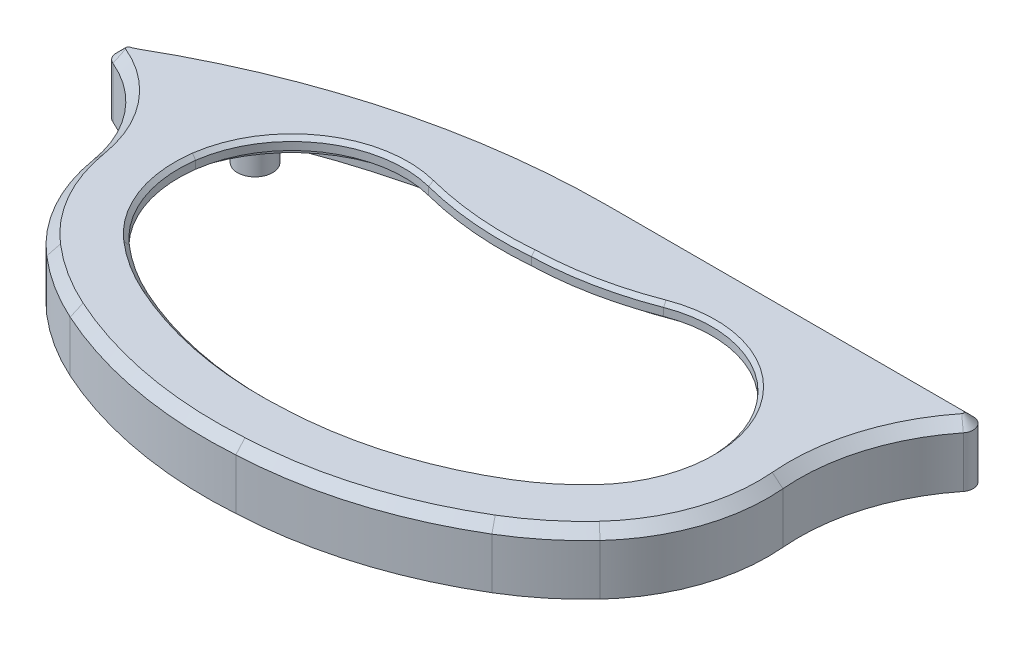
SolidWorks part; units mm, degrees
ref_plane "Front Plane" through (0, 0, 0) normal (0, 0, 1) x (1, 0, 0)
ref_plane "Top Plane" through (0, 0, 0) normal (0, 1, 0) x (1, 0, 0)
ref_plane "Right Plane" through (0, 0, 0) normal (1, 0, 0) x (0, 0, -1)
sketch "Case_Line" plane through (0, 0, 0) normal (0, 1, 0) x (1, 0, 0)
  line L0 (80.0987, 83.4768) -> (-10.614, 83.4768) construction
  arc A0 (85.0987, 88.4768) -> (80.0987, 83.4768) centre (80.0987, 88.4768) cw construction
  arc A2 (-113.6793, 59.6258) -> (-106.8525, 57.7833) centre (-109.3447, 62.1179) ccw construction
  arc A6 (-10.614, 83.4768) -> (-106.8525, 57.7833) centre (-10.614, -109.6066) ccw construction
sketch "Wrest" plane through (0, 0, 0) normal (0, 1, 0) x (1, 0, 0)
  line L6 (-10.569, 65.8598) -> (-6.2316, -9.4162) construction
  line L7 (-10.569, 65.8598) -> (16.1282, 71.2217) construction
  line L8 (16.1282, 71.2217) -> (60.9608, 48.0555) construction
  line L9 (60.9608, 48.0555) -> (52.5888, 15.0143) construction
  line L10 (52.5888, 15.0143) -> (39.5302, 4.389) construction
  line L11 (39.5302, 4.389) -> (-6.2316, -9.4162) construction
  line L14 (80.0987, 83.4768) -> (-10.614, 83.4768) construction
  line L19 (-74.9013, 38.0401) -> (-74.9013, -63.0808) construction
  line L21 (-74.9013, 105.4768) -> (-74.9013, 87.4768) construction
  arc A10 (-10.569, 65.8598) -> (16.1282, 71.2217) centre (-12.89, 146.5605) ccw construction
  arc A11 (16.1282, 71.2217) -> (60.9608, 48.0555) centre (28.2576, 39.7306) cw construction
  arc A12 (60.9608, 48.0555) -> (52.5888, 15.0143) centre (26.348, 39.2445) cw construction
  arc A13 (52.5888, 15.0143) -> (39.5302, 4.389) centre (8.9509, 55.3086) cw construction
  arc A14 (39.5302, 4.389) -> (-6.2316, -9.4162) centre (-10.6307, 87.9151) cw construction
  arc A15 (-53.2763, -0.9584) -> (-6.2316, -9.4162) centre (-13.0408, 87.7763) ccw construction
  arc A16 (-67.4688, 8.0967) -> (-53.2763, -0.9584) centre (-28.7477, 53.1364) ccw construction
  arc A17 (-79.5804, 39.9577) -> (-67.4688, 8.0967) centre (-44.1846, 35.1805) ccw construction
  arc A18 (-37.7053, 68.1198) -> (-79.5804, 39.9577) centre (-46.1374, 35.444) ccw construction
  arc A19 (-10.569, 65.8598) -> (-37.7053, 68.1198) centre (-17.5323, 146.293) cw construction
  arc A20 (12.5339, 80.5534) -> (70.6518, 50.5225) centre (28.2576, 39.7306) cw construction
  arc A24 (-10.2812, 60.8661) -> (17.9253, 66.5558) centre (-12.89, 146.5605) ccw
  arc A50 (70.6518, 50.5225) -> (59.9357, 8.2303) centre (26.348, 39.2445) cw construction
  arc A51 (59.9357, 8.2303) -> (44.6786, -4.1838) centre (8.9509, 55.3086) cw construction
  arc A53 (44.6786, -4.1838) -> (-5.6564, -19.4003) centre (-10.6307, 87.9151) cw construction
  arc A54 (-57.4059, -10.0658) -> (-5.6564, -19.4003) centre (-13.0408, 87.7763) ccw construction
  arc A58 (-73.9879, 0.5138) -> (-57.4059, -10.0658) centre (-28.7477, 53.1364) ccw construction
  arc A71 (17.9253, 66.5558) -> (56.1154, 46.8221) centre (28.2576, 39.7306) cw
  arc A72 (56.1154, 46.8221) -> (48.9153, 18.4063) centre (26.348, 39.2445) cw
  arc A73 (48.9153, 18.4063) -> (36.9561, 8.6755) centre (8.9509, 55.3086) cw
  arc A74 (36.9561, 8.6755) -> (-6.5193, -4.424) centre (-10.6307, 87.9151) cw
  arc A75 (-51.2115, 3.5954) -> (-6.5193, -4.424) centre (-13.0408, 87.7763) ccw
  arc A76 (-64.2092, 11.8882) -> (-51.2115, 3.5954) centre (-28.7477, 53.1364) ccw
  arc A77 (-74.6253, 39.2889) -> (-64.2092, 11.8882) centre (-44.1846, 35.1805) ccw
  arc A78 (-38.9546, 63.2784) -> (-74.6253, 39.2889) centre (-46.1374, 35.444) ccw
  arc A79 (-10.2812, 60.8661) -> (-38.9546, 63.2784) centre (-17.5323, 146.293) cw
  arc A80 (-89.4906, 41.2952) -> (-73.9879, 0.5138) centre (-44.1846, 35.1805) ccw construction
  arc A81 (-35.2066, 77.8026) -> (-89.4906, 41.2952) centre (-46.1374, 35.444) ccw construction
  arc A82 (-11.1445, 75.8479) -> (-35.2066, 77.8026) centre (-17.5323, 146.293) cw construction
  arc A83 (-11.1445, 75.8479) -> (12.5339, 80.5534) centre (-12.89, 146.5605) ccw construction
  arc A85 (-10.614, 83.4768) -> (-106.8525, 57.7833) centre (-10.614, -109.6066) ccw construction
  dimension "D2" = 27.2303
  dimension "D7" = 80.7341
  dimension "D15" = 5
  dimension "D1" = 75.4008
  dimension "D3" = 50.4642
  dimension "D4" = 34.0854
  dimension "D5" = 47.7989
  dimension "D6" = 16.8352
  dimension "D8" = 103.108
  dimension "D9" = 98.059
  dimension "D10" = 76.51
  dimension "D11" = 10
sketch "Sketch6" plane through (0, 0, 0) normal (0, 1, 0) x (1, 0, 0)
  line L0 (84.9594, 87.3051) -> (70.7917, 28.5311) construction
  line L1 (-88.1859, 17.3185) -> (-113.6272, 59.5372) construction
  line L2 (80.0987, 83.4768) -> (-10.614, 83.4768)
  arc A0 (-73.9879, 0.5138) -> (-57.4059, -10.0658) centre (-28.7477, 53.1364) ccw construction
  arc A1 (59.9357, 8.2303) -> (70.6518, 50.5225) centre (26.348, 39.2445) ccw construction
  arc A2 (-113.6793, 59.6258) -> (-106.8525, 57.7833) centre (-109.3447, 62.1179) ccw construction
  arc A3 (80.0987, 83.4768) -> (85.0987, 88.4768) centre (80.0987, 88.4768) ccw construction
  arc A4 (80.1793, 83.4775) -> (82.5748, 78.6094) centre (80.2278, 80.4779) cw
  arc A5 (-107.9166, 57.3262) -> (-108.2193, 51.6843) centre (-107.0597, 54.4512) ccw
  circle A6 centre (80.2278, 80.4779) radius 3 construction
  arc A7 (-5.6564, -19.4003) -> (44.6786, -4.1838) centre (-10.6307, 87.9151) ccw construction
  arc A8 (59.9357, 8.2303) -> (71.8718, 43.1263) centre (26.4104, 39.1869) ccw
  arc A9 (82.5748, 78.6094) -> (71.8718, 43.1263) centre (121.7206, 47.4458) ccw
  circle A10 centre (-107.0597, 54.4512) radius 3 construction
  arc A11 (-57.4059, -10.0658) -> (-5.6564, -19.4003) centre (-13.0408, 87.7763) ccw construction
  arc A12 (-108.2193, 51.6843) -> (-89.2905, 27.7324) centre (-120.4115, 22.5936) cw
  arc A13 (-89.4906, 41.2952) -> (-73.9879, 0.5138) centre (-44.1846, 35.1805) ccw construction
  arc A14 (-73.9879, 0.5138) -> (-89.2905, 27.7324) centre (-44.1846, 35.1805) cw
  arc A15 (-73.9879, 0.5138) -> (-57.4059, -10.0658) centre (-28.7477, 53.1364) ccw
  arc A16 (80.1793, 83.4775) -> (80.0987, 83.4768) centre (80.0987, 88.4768) cw
  arc A21 (-57.4059, -10.0658) -> (-5.6564, -19.4003) centre (-13.0408, 87.7763) ccw
  arc A22 (59.9357, 8.2303) -> (44.6786, -4.1838) centre (8.9509, 55.3086) cw
  arc A23 (44.6786, -4.1838) -> (-5.6564, -19.4003) centre (-10.6307, 87.9151) cw
  arc A24 (70.6518, 50.5225) -> (12.5339, 80.5534) centre (28.2576, 39.7306) ccw construction
  arc A25 (-107.9166, 57.3262) -> (-106.8525, 57.7833) centre (-109.3447, 62.1179) ccw
  arc A26 (-106.8525, 57.7833) -> (-10.614, 83.4768) centre (-10.614, -109.6066) cw
  dimension "D1" = 3
extrude "Top_plane" add sketch "Sketch6" against normal blind 3
sketch "Sketch9" plane through (0, 0, 0) normal (0, 1, 0) x (1, 0, 0)
  arc A20 (-10.2812, 60.8661) -> (17.9253, 66.5558) centre (-12.89, 146.5605) ccw
  arc A21 (56.1154, 46.8221) -> (17.9253, 66.5558) centre (28.2576, 39.7306) ccw
  arc A22 (48.9153, 18.4063) -> (56.1154, 46.8221) centre (26.348, 39.2445) ccw
  arc A23 (36.9561, 8.6755) -> (48.9153, 18.4063) centre (8.9509, 55.3086) ccw
  arc A24 (-6.5193, -4.424) -> (36.9561, 8.6755) centre (-10.6307, 87.9151) ccw
  arc A25 (-51.2115, 3.5954) -> (-6.5193, -4.424) centre (-13.0408, 87.7763) ccw
  arc A26 (-64.2092, 11.8882) -> (-51.2115, 3.5954) centre (-28.7477, 53.1364) ccw
  arc A27 (-74.6253, 39.2889) -> (-64.2092, 11.8882) centre (-44.1846, 35.1805) ccw
  arc A28 (-38.9546, 63.2784) -> (-74.6253, 39.2889) centre (-46.1374, 35.444) ccw
  arc A29 (-38.9546, 63.2784) -> (-10.2812, 60.8661) centre (-17.5323, 146.293) ccw
  arc A30 (-10.2812, 60.8661) -> (17.9253, 66.5558) centre (-12.89, 146.5605) ccw
  arc A31 (56.1154, 46.8221) -> (17.9253, 66.5558) centre (28.2576, 39.7306) ccw
  arc A32 (48.9153, 18.4063) -> (56.1154, 46.8221) centre (26.348, 39.2445) ccw
  arc A33 (36.9561, 8.6755) -> (48.9153, 18.4063) centre (8.9509, 55.3086) ccw
  arc A34 (-6.5193, -4.424) -> (36.9561, 8.6755) centre (-10.6307, 87.9151) ccw
  arc A35 (-51.2115, 3.5954) -> (-6.5193, -4.424) centre (-13.0408, 87.7763) ccw
  arc A36 (-64.2092, 11.8882) -> (-51.2115, 3.5954) centre (-28.7477, 53.1364) ccw
  arc A37 (-74.6253, 39.2889) -> (-64.2092, 11.8882) centre (-44.1846, 35.1805) ccw
  arc A38 (-38.9546, 63.2784) -> (-74.6253, 39.2889) centre (-46.1374, 35.444) ccw
  arc A39 (-38.9546, 63.2784) -> (-10.2812, 60.8661) centre (-17.5323, 146.293) ccw
  dimension "D1" = 0
extrude "Pillow_hole" cut sketch "Sketch9" against normal through all
chamfer "Pillow_chamfer" distance 1 angle 45 10 edges at (16.0353, 0, 0.5854) (43.2822, 0, -13.115) (56.1237, 0, -31.6999) (4.0625, 0, -62.5191) (41.4538, 0, -65.2689) (-29.3655, 0, 3.2014) (-58.0057, 0, -7.2789) (-24.7198, 0, -60.8607) (-72.8968, 0, -24.2659) (-62.1796, 0, -59.2977)
sketch "Sketch7" plane through (0, -3, 0) normal (0, -1, 0) x (1, 0, 0)
  line L3 (-10.614, -83.4768) -> (80.0987, -83.4768)
  line L4 (-10.614, -83.4768) -> (80.0987, -83.4768)
  arc A37 (-106.8525, -57.7833) -> (-10.614, -83.4768) centre (-10.614, 109.6066) ccw
  arc A38 (-106.8525, -57.7833) -> (-107.9166, -57.3262) centre (-109.3447, -62.1179) ccw
  arc A39 (-108.2193, -51.6843) -> (-107.9166, -57.3262) centre (-107.0597, -54.4512) ccw
  arc A40 (-108.2193, -51.6843) -> (-89.2905, -27.7324) centre (-120.4115, -22.5936) ccw
  arc A41 (-73.9879, -0.5138) -> (-89.2905, -27.7324) centre (-44.1846, -35.1805) ccw
  arc A42 (-57.4059, 10.0658) -> (-73.9879, -0.5138) centre (-28.7477, -53.1364) ccw
  arc A43 (-5.6564, 19.4003) -> (-57.4059, 10.0658) centre (-13.0408, -87.7763) ccw
  arc A44 (44.6786, 4.1838) -> (-5.6564, 19.4003) centre (-10.6307, -87.9151) ccw
  arc A45 (59.9357, -8.2303) -> (44.6786, 4.1838) centre (8.9509, -55.3086) ccw
  arc A46 (71.8718, -43.1263) -> (59.9357, -8.2303) centre (26.4104, -39.1869) ccw
  arc A47 (71.8718, -43.1263) -> (82.5748, -78.6094) centre (121.7206, -47.4458) ccw
  arc A48 (80.1793, -83.4775) -> (82.5748, -78.6094) centre (80.2278, -80.4779) ccw
  arc A49 (80.1793, -83.4775) -> (80.0987, -83.4768) centre (80.0987, -88.4768) ccw
  arc A50 (-106.8525, -57.7833) -> (-10.614, -83.4768) centre (-10.614, 109.6066) ccw
  arc A51 (-106.8525, -57.7833) -> (-107.9166, -57.3262) centre (-109.3447, -62.1179) ccw
  arc A52 (-108.2193, -51.6843) -> (-107.9166, -57.3262) centre (-107.0597, -54.4512) ccw
  arc A53 (-108.2193, -51.6843) -> (-89.2905, -27.7324) centre (-120.4115, -22.5936) ccw
  arc A54 (-73.9879, -0.5138) -> (-89.2905, -27.7324) centre (-44.1846, -35.1805) ccw
  arc A55 (-57.4059, 10.0658) -> (-73.9879, -0.5138) centre (-28.7477, -53.1364) ccw
  arc A56 (-5.6564, 19.4003) -> (-57.4059, 10.0658) centre (-13.0408, -87.7763) ccw
  arc A57 (44.6786, 4.1838) -> (-5.6564, 19.4003) centre (-10.6307, -87.9151) ccw
  arc A58 (59.9357, -8.2303) -> (44.6786, 4.1838) centre (8.9509, -55.3086) ccw
  arc A59 (71.8718, -43.1263) -> (59.9357, -8.2303) centre (26.4104, -39.1869) ccw
  arc A60 (71.8718, -43.1263) -> (82.5748, -78.6094) centre (121.7206, -47.4458) ccw
  arc A61 (80.1793, -83.4775) -> (82.5748, -78.6094) centre (80.2278, -80.4779) ccw
  arc A62 (80.1793, -83.4775) -> (80.0987, -83.4768) centre (80.0987, -88.4768) ccw
  arc A188 (-53.2763, 0.9584) -> (-67.4688, -8.0967) centre (-28.7477, -53.1364) ccw
  arc A189 (-6.2316, 9.4162) -> (-53.2763, 0.9584) centre (-13.0408, -87.7763) ccw
  arc A190 (39.5302, -4.389) -> (-6.2316, 9.4162) centre (-10.6307, -87.9151) ccw
  arc A191 (52.5888, -15.0143) -> (39.5302, -4.389) centre (8.9509, -55.3086) ccw
  arc A192 (60.9608, -48.0555) -> (52.5888, -15.0143) centre (26.348, -39.2445) ccw
  arc A193 (16.1282, -71.2217) -> (60.9608, -48.0555) centre (28.2576, -39.7306) ccw
  arc A194 (16.1282, -71.2217) -> (-10.569, -65.8598) centre (-12.89, -146.5605) ccw
  arc A195 (-10.569, -65.8598) -> (-37.7053, -68.1198) centre (-17.5323, -146.293) ccw
  arc A196 (-79.5804, -39.9577) -> (-37.7053, -68.1198) centre (-46.1374, -35.444) ccw
  arc A197 (-67.4688, -8.0967) -> (-79.5804, -39.9577) centre (-44.1846, -35.1805) ccw
  arc A198 (-53.2763, 0.9584) -> (-67.4688, -8.0967) centre (-28.7477, -53.1364) ccw
  arc A199 (-6.2316, 9.4162) -> (-53.2763, 0.9584) centre (-13.0408, -87.7763) ccw
  arc A200 (39.5302, -4.389) -> (-6.2316, 9.4162) centre (-10.6307, -87.9151) ccw
  arc A201 (52.5888, -15.0143) -> (39.5302, -4.389) centre (8.9509, -55.3086) ccw
  arc A202 (60.9608, -48.0555) -> (52.5888, -15.0143) centre (26.348, -39.2445) ccw
  arc A203 (16.1282, -71.2217) -> (60.9608, -48.0555) centre (28.2576, -39.7306) ccw
  arc A204 (16.1282, -71.2217) -> (-10.569, -65.8598) centre (-12.89, -146.5605) ccw
  arc A205 (-10.569, -65.8598) -> (-37.7053, -68.1198) centre (-17.5323, -146.293) ccw
  arc A206 (-79.5804, -39.9577) -> (-37.7053, -68.1198) centre (-46.1374, -35.444) ccw
  arc A207 (-67.4688, -8.0967) -> (-79.5804, -39.9577) centre (-44.1846, -35.1805) ccw
  dimension "D1" = 0
  dimension "D2" = 0
extrude "Wrest_socket" add sketch "Sketch7" along normal blind 4
sketch "Sketch8" plane through (0, -7, 0) normal (0, -1, 0) x (1, 0, 0)
  line L2 (-10.614, -81.4768) -> (80.0987, -81.4768)
  line L6 (-10.614, -83.4768) -> (80.0987, -83.4768)
  line L7 (-10.614, -83.4768) -> (80.0987, -83.4768)
  arc A45 (80.2116, -81.4778) -> (80.0987, -81.4768) centre (80.0987, -88.4768) ccw
  arc A46 (80.2116, -81.4778) -> (81.0101, -79.8551) centre (80.2278, -80.4779) ccw
  arc A47 (69.8793, -42.9536) -> (81.0101, -79.8551) centre (121.7206, -47.4458) ccw
  arc A48 (69.8793, -42.9536) -> (58.4664, -9.5871) centre (26.4104, -39.1869) ccw
  arc A49 (58.4664, -9.5871) -> (43.6489, 2.4693) centre (8.9509, -55.3086) ccw
  arc A50 (43.6489, 2.4693) -> (-5.7714, 17.4035) centre (-10.6307, -87.9151) ccw
  arc A51 (-5.7714, 17.4035) -> (-56.58, 8.2443) centre (-13.0408, -87.7763) ccw
  arc A52 (-56.58, 8.2443) -> (-72.6841, -2.0304) centre (-28.7477, -53.1364) ccw
  arc A53 (-72.6841, -2.0304) -> (-87.3173, -28.0582) centre (-44.1846, -35.1805) ccw
  arc A54 (-107.4463, -53.5289) -> (-87.3173, -28.0582) centre (-120.4115, -22.5936) ccw
  arc A55 (-107.4463, -53.5289) -> (-107.3453, -55.4095) centre (-107.0597, -54.4512) ccw
  arc A56 (-105.8557, -56.0494) -> (-107.3453, -55.4095) centre (-109.3447, -62.1179) ccw
  arc A57 (-105.8557, -56.0494) -> (-10.614, -81.4768) centre (-10.614, 109.6066) ccw
  arc A58 (-106.8525, -57.7833) -> (-10.614, -83.4768) centre (-10.614, 109.6066) ccw
  arc A59 (-106.8525, -57.7833) -> (-107.9166, -57.3262) centre (-109.3447, -62.1179) ccw
  arc A60 (-108.2193, -51.6843) -> (-107.9166, -57.3262) centre (-107.0597, -54.4512) ccw
  arc A61 (-108.2193, -51.6843) -> (-89.2905, -27.7324) centre (-120.4115, -22.5936) ccw
  arc A62 (-73.9879, -0.5138) -> (-89.2905, -27.7324) centre (-44.1846, -35.1805) ccw
  arc A63 (-57.4059, 10.0658) -> (-73.9879, -0.5138) centre (-28.7477, -53.1364) ccw
  arc A64 (-5.6564, 19.4003) -> (-57.4059, 10.0658) centre (-13.0408, -87.7763) ccw
  arc A65 (44.6786, 4.1838) -> (-5.6564, 19.4003) centre (-10.6307, -87.9151) ccw
  arc A66 (59.9357, -8.2303) -> (44.6786, 4.1838) centre (8.9509, -55.3086) ccw
  arc A67 (71.8718, -43.1263) -> (59.9357, -8.2303) centre (26.4104, -39.1869) ccw
  arc A68 (71.8718, -43.1263) -> (82.5748, -78.6094) centre (121.7206, -47.4458) ccw
  arc A69 (80.1793, -83.4775) -> (82.5748, -78.6094) centre (80.2278, -80.4779) ccw
  arc A70 (80.1793, -83.4775) -> (80.0987, -83.4768) centre (80.0987, -88.4768) ccw
  arc A71 (-106.8525, -57.7833) -> (-10.614, -83.4768) centre (-10.614, 109.6066) ccw
  arc A72 (-106.8525, -57.7833) -> (-107.9166, -57.3262) centre (-109.3447, -62.1179) ccw
  arc A73 (-108.2193, -51.6843) -> (-107.9166, -57.3262) centre (-107.0597, -54.4512) ccw
  arc A74 (-108.2193, -51.6843) -> (-89.2905, -27.7324) centre (-120.4115, -22.5936) ccw
  arc A75 (-73.9879, -0.5138) -> (-89.2905, -27.7324) centre (-44.1846, -35.1805) ccw
  arc A76 (-57.4059, 10.0658) -> (-73.9879, -0.5138) centre (-28.7477, -53.1364) ccw
  arc A77 (-5.6564, 19.4003) -> (-57.4059, 10.0658) centre (-13.0408, -87.7763) ccw
  arc A78 (44.6786, 4.1838) -> (-5.6564, 19.4003) centre (-10.6307, -87.9151) ccw
  arc A79 (59.9357, -8.2303) -> (44.6786, 4.1838) centre (8.9509, -55.3086) ccw
  arc A80 (71.8718, -43.1263) -> (59.9357, -8.2303) centre (26.4104, -39.1869) ccw
  arc A81 (71.8718, -43.1263) -> (82.5748, -78.6094) centre (121.7206, -47.4458) ccw
  arc A82 (80.1793, -83.4775) -> (82.5748, -78.6094) centre (80.2278, -80.4779) ccw
  arc A83 (80.1793, -83.4775) -> (80.0987, -83.4768) centre (80.0987, -88.4768) ccw
  dimension "D1" = 0
  dimension "D2" = 2
extrude "Wall" add sketch "Sketch8" along normal blind 8.5
chamfer "Main_chamfer" distance 2.5 angle 45 14 edges at (-110.0554, 0, -54.6119) (-32.1111, 0, 17.9482) (20.4565, 0, 14.9193) (52.7492, 0, -1.4799) (82.9195, 0, -81.8024) (80.139, 0, -83.477) (34.7423, 0, -83.4768) (-95.6642, 0, -42.1509) (-84.0351, 0, -12.7761) (-66.0737, 0, 5.3665) (69.5863, 0, -24.4187) (73.8168, 0, -61.8954) (-60.4187, 0, -76.9429) (-107.3713, 0, -57.5238)
sketch "Sketch10" plane through (0, -7, 0) normal (0, -1, 0) x (1, 0, 0)
  line L0 (-10.2812, -60.8661) -> (-6.5193, 4.424) construction
  line L1 (-78, -57.8598) -> (-8.4002, -28.221) construction
  line L2 (-8.4002, -28.221) -> (47.5551, -4.3927) construction
  circle A0 centre (-78, -57.8598) radius 4.5
  circle A1 centre (-78, -57.8598) radius 1.35
  circle A2 centre (47.5551, -4.3927) radius 4.5
  circle A3 centre (47.5551, -4.3927) radius 1.35
  arc A5 (52.5888, -15.0143) -> (39.5302, -4.389) centre (8.9509, -55.3086) ccw construction
  dimension "D1" = 9
  dimension "D2" = 2.7
  dimension "D3" = 78
  dimension "D4" = 8
extrude "Boss-Extrude1" add sketch "Sketch10" along normal blind 5.5
sketch "Sketch13" plane through (0, -12.5, 0) normal (0, -1, 0) x (1, 0, 0)
  line L1 (-76.4989, -60.4598) -> (-74.9978, -57.8598)
  line L2 (-74.9978, -57.8598) -> (-76.4989, -55.2598)
  line L3 (-76.4989, -55.2598) -> (-79.5011, -55.2598)
  line L4 (-79.5011, -55.2598) -> (-81.0022, -57.8598)
  line L5 (-81.0022, -57.8598) -> (-79.5011, -60.4598)
  line L6 (-79.5011, -60.4598) -> (-76.4989, -60.4598)
  line L7 (49.0562, -6.9927) -> (50.5573, -4.3927)
  line L8 (50.5573, -4.3927) -> (49.0562, -1.7927)
  line L9 (49.0562, -1.7927) -> (46.054, -1.7927)
  line L10 (46.054, -1.7927) -> (44.5529, -4.3927)
  line L11 (44.5529, -4.3927) -> (46.054, -6.9927)
  line L12 (46.054, -6.9927) -> (49.0562, -6.9927)
  circle A0 centre (-78, -57.8598) radius 2.6 construction
  circle A1 centre (47.5551, -4.3927) radius 2.6 construction
  dimension "D1" = 5.2
extrude "Nut_holes" cut sketch "Sketch13" against normal blind 3
ref_plane "Magnet01-Plane1" through (-51.514, 0, -89.5994) normal (-0.4984, 0, -0.8669) x (-0.8669, 0, 0.4984)
ref_plane "Magnet01-Plane2" through (-50.5171, 0, -87.8656) normal (0.4984, 0, 0.8669) x (0.8669, 0, -0.4984)
sketch "Sketch11" plane through (-50.5171, 0, -87.8656) normal (0.4984, 0, 0.8669) x (0.8669, 0, -0.4984)
  line L0 (-63.8328, -15.5) -> (-63.8328, -2.5) construction
  line L2 (-63.8328, -15.5) -> (32.4057, -15.5) construction
  circle A0 centre (-53.8328, -7.5) radius 3
  dimension "D3" = 6
  dimension "D1" = 10
  dimension "D2" = 8
extrude "Magnet01" cut sketch "Sketch11" along normal blind 5.2 contours A0
sketch "Sketch12" plane through (0, 0, -81.4768) normal (0, 0, -1) x (-1, 0, 0)
  line L1 (-80.0987, -15.5) -> (-80.0987, -2.5) construction
  line L2 (10.614, -15.5) -> (-80.0987, -15.5) construction
  circle A0 centre (-70.0987, -7.5) radius 3
  dimension "D1" = 6
  dimension "D2" = 8
  dimension "D3" = 10
extrude "Magnet02" cut sketch "Sketch12" against normal blind 5.2
